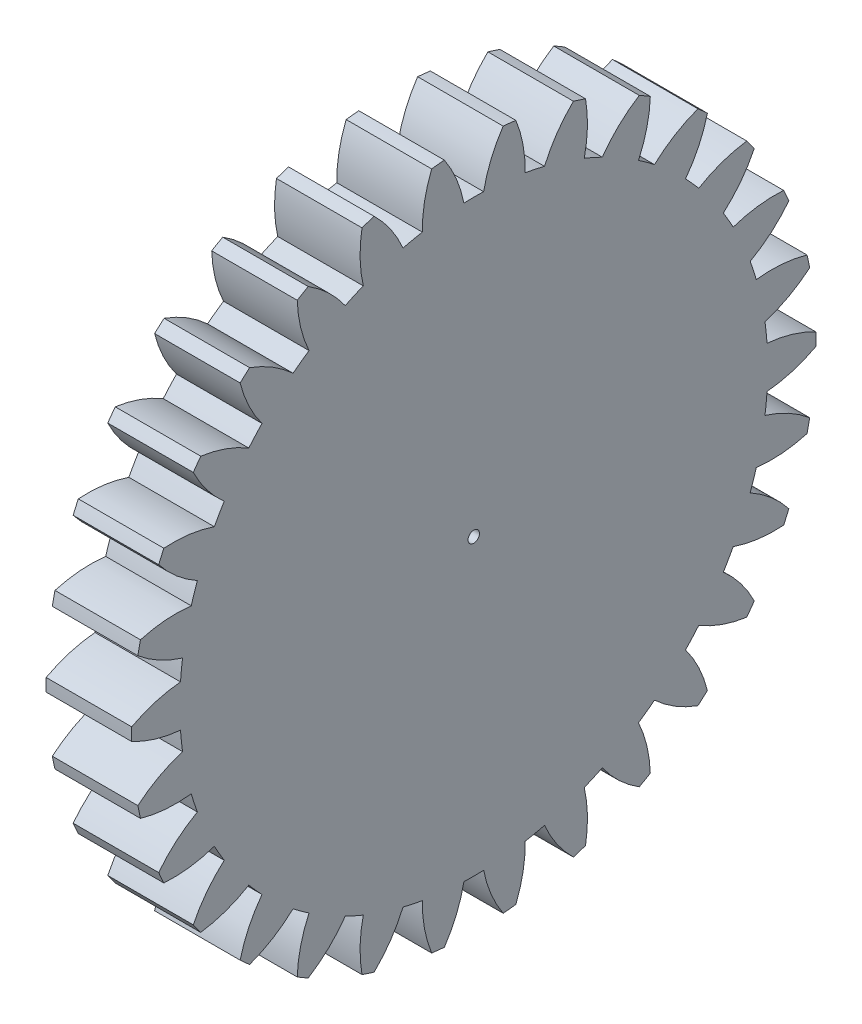
SolidWorks part; units mm, degrees
ref_plane "Plane1" through (0, 0, 0) normal (0, 0, 1) x (1, 0, 0)
ref_plane "Plane2" through (0, 0, 0) normal (0, 1, 0) x (1, 0, 0)
ref_plane "Plane3" through (0, 0, 0) normal (1, 0, 0) x (0, 0, -1)
sketch "HoldingSke" plane through (0, 0, 0) normal (0, 1, 0) x (1, 0, 0)
  line L0 (0, 0) -> (0.5774, -0.3333)
  line L1 (-15, 0) -> (100, 0) construction
  line L2 (0, 0) -> (-2.1039, 2.3779)
  line L3 (0, 0) -> (-11.863, 4.5341)
  line L4 (0, 0) -> (7.479, 4.318)
  line L5 (0, 0) -> (-46.8476, -17.4728)
  line L6 (0, 0) -> (-4.9738, -3.3558)
  line L7 (-2.1039, 2.3779) -> (8.6586, 51.2059)
  line L8 (-76.2, 54.61) -> (-76.1, 54.61)
  line L9 (-71.009, 38.7566) -> (-53.1078, 45.2721)
  line L10 (-76.2, 71.12) -> (104.1128, 71.12)
  line L11 (0, 0) -> (-6, 0)
  line L12 (-76.2, 101.6) -> (-76.147, 101.6)
  line L13 (24.9733, 27.94) -> (52.9518, 28.4284)
  line L14 (24.9733, 27.94) -> (24.9743, 27.94)
  line L15 (24.9733, 27.94) -> (100.4006, 29.5858)
  line L16 (-63.627, -1.5) -> (-12.827, -1.5)
  circle A0 centre (0, 0) radius 0.4
  circle A1 centre (0, 0) radius 20.624
  circle A2 centre (0, 0) radius 37.5
  circle A3 centre (0, 0) radius 0.4
  dimension "MHD" = 41.248
  dimension "Hub_dia" = 75
  dimension "Bore" = 0.8
  dimension "MBD" = 0.8
  dimension "Num_teeth" = 30
  dimension "Pitch_radius" = 180.3128
  dimension "Pitch" = 0.6667
  dimension "Width" = 6
  dimension "Overall_len" = 50
  dimension "Show_teeth" = 30
  dimension "Thickness" = 6
  dimension "OAL" = 50.0001
  dimension "T_dim" = 0.1
  dimension "Ap" = 20
  dimension "H" = 19.05
  dimension "Backlash" = 0.053
  dimension "Addendum_fac" = 1
  dimension "Dedendum_fac" = 1.25
  dimension "Clearance_fac" = 0.25
  dimension "Dedendum_add" = 0.001
  dimension "Module" = 1.5
sketch "BasProSke" plane through (0, 0, 0) normal (0, 1, 0) x (1, 0, 0)
  line L0 (-10, 0) -> (60, 0) construction
  line L1 (0, 0) -> (0, 24)
  line L2 (0, 0) -> (6, 0)
  line L3 (6, 0) -> (6, 24)
  line L4 (6, 24) -> (0, 24)
  dimension "Diameter" = 48
  dimension "Thickness" = 6
revolve "Base-Revolve" add sketch "BasProSke" angle 360 about L0
sketch "TooCutSke" plane through (0, 0, 0) normal (1, 0, 0) x (0, 0, -1)
  line L1 (0, 0) -> (0, 107) construction
  line L2 (0, 0) -> (-1.2703, 22.4641) construction
  line L3 (0, 0) -> (-4.6983, 44.7014) construction
  line L4 (-1.2703, 22.4641) -> (-2.3492, 22.3507) construction
  arc A0 (0.6933, 20.6123) -> (-0.6933, 20.6123) centre (0, 0) ccw
  arc A1 (2.0805, 23.9351) -> (-2.0805, 23.9351) centre (0, 0) ccw
  circle A2 centre (0, 0) radius 22.5 construction
  circle A3 centre (0, 0) radius 21.1431 construction
  arc A4 (-0.6933, 20.6123) -> (-2.0805, 23.9351) centre (-9.5243, 18.8764) ccw
  arc A5 (2.0805, 23.9351) -> (0.6933, 20.6123) centre (9.5243, 18.8764) ccw
  dimension "Root_dia" = 41.248
  dimension "Overcut_dia" = 48.0508
  dimension "Pitch_dia" = 45
  dimension "Base_dia" = 42.2862
  dimension "Flank_rad" = 9
  dimension "Half_ang" = 6
  dimension "Half_CT" = 1.0848
extrude "ToothCut" cut sketch "TooCutSke" along normal through all
fillet "Breaks" [suppressed] radius 0.03 tangent propagation no
fillet "RootFillets" [suppressed] radius 0.376
pattern_circular "TeethCuts" count 30 every 12 about axis through (-10, 0, 0) along (1, 0, 0) of "ToothCut", "RootFillets", "Breaks"
sketch "HubNeaOneSke" plane through (0, 0, 0) normal (-1, 0, 0) x (0, 0, 1)
  circle A0 centre (0, 0) radius 20.624
  dimension "Diameter" = 41.248
extrude "HubNearOne" [suppressed] add sketch "HubNeaOneSke" along normal blind 44.0001
sketch "HubNeaBotSke" plane through (0, 0, 0) normal (-1, 0, 0) x (0, 0, 1)
  circle A0 centre (0, 0) radius 20.624
  dimension "Diameter" = 41.248
extrude "HubNearBoth" [suppressed] add sketch "HubNeaBotSke" along normal blind 22
ref_plane "FarPln" through (6, 0, 0) normal (1, 0, 0) x (0, 0, -1)
sketch "HubFarSke" plane through (6, 0, 0) normal (1, 0, 0) x (0, 0, -1)
  circle A0 centre (0, 0) radius 20.624
  dimension "Diameter" = 41.248
extrude "HubFar" [suppressed] add sketch "HubFarSke" along normal blind 22
sketch "BorSke" plane through (0, 0, 0) normal (1, 0, 0) x (0, 0, -1)
  circle A0 centre (0, 0) radius 0.4
  dimension "Diameter" = 0.8
extrude "Bore" cut sketch "BorSke" along normal mid plane 100.0001
sketch "KeySke" plane through (0, 0, 0) normal (1, 0, 0) x (0, 0, -1)
  line L0 (-0.05, 0) -> (-0.05, 0.5)
  line L1 (-0.05, 0.5) -> (0.05, 0.5)
  line L2 (0.05, 0.5) -> (0.05, 0)
  line L3 (0, 0) -> (0, 34) construction
  line L4 (-0.05, 0) -> (0.05, 0)
  dimension "Offset" = 0.5
  dimension "Width" = 0.1
extrude "Keyway" [suppressed] cut sketch "KeySke" along normal mid plane 100.0001
pattern_circular "Keyway2" [suppressed] count 2 every 90 about axis through (-10, 0, 0) along (1, 0, 0)
equation "' \"Module@HoldingSke\" = 6.35"
equation "' \"Num_teeth@HoldingSke\" = 12"
equation "' \"Ap@HoldingSke\" =  20"
equation "' \"Width@HoldingSke\" = 0.5 * 25.4"
equation "' \"Hub_dia@HoldingSke\"= 1 * 25.4"
equation "' \"Overall_len@HoldingSke\" = 1.0 * 25.4"
equation "' \"Bore@HoldingSke\" = 0.75 * 25.4"
equation "' \"T_dim@HoldingSke\" = 0.1 * 25.4"
equation "' \"Width@KeySke\" = 0.25 * 25.4"
equation "' \"Show_teeth@HoldingSke\" = 13"
equation "' \"Backlash@HoldingSke\" = 0.009 * 25.4"
equation "' \"Addendum_fac@HoldingSke\" = 1.0"
equation "' \"Dedendum_fac@HoldingSke\" = 1.25"
equation "' \"Dedendum_add@HoldingSke\" = 0.00005 * 25.4"
equation "' \"Clearance_fac@HoldingSke\" = 0.25"
equation "\"Pitch@HoldingSke\" = 1 / \"Module@HoldingSke\""
equation "\"Overcut_dia@TooCutSke\" = (\"Num_teeth@HoldingSke\" + 2 * \"Addendum_fac@HoldingSke\") / \"Pitch@HoldingSke\" + 0.002 * 25.4"
equation "\"Pitch_dia@TooCutSke\" = \"Num_teeth@HoldingSke\" / \"Pitch@HoldingSke\""
equation "\"Base_dia@TooCutSke\" = \"Num_teeth@HoldingSke\" / \"Pitch@HoldingSke\" * cos((\"Ap@HoldingSke\"  * 3.14159265 / 180))"
equation "\"Root_dia@TooCutSke\" = (\"Num_teeth@HoldingSke\" + 2) / \"Pitch@HoldingSke\" - 2 * (\"Addendum_fac@HoldingSke\" + \"Dedendum_fac@HoldingSke\") / \"Pitch@HoldingSke\" - \"Dedendum_add@HoldingSke\" * 2"
equation "\"Half_ang@TooCutSke\" = 180 / \"Num_teeth@HoldingSke\""
equation "\"Half_CT@TooCutSke\" = \"Num_teeth@HoldingSke\" / \"Pitch@HoldingSke\" * sin((3.14159265 / 2 / \"Num_teeth@HoldingSke\")) / 2 - 7 * \"Backlash@HoldingSke\" / 4"
equation "\"Flank_rad@TooCutSke\" = \"Num_teeth@HoldingSke\" / \"Pitch@HoldingSke\" / 5"
equation "\"Radius@RootFillets\" = \"Clearance_fac@HoldingSke\" / \"Pitch@HoldingSke\" + \"Dedendum_add@HoldingSke\""
equation "\"Break_rad@Breaks\" = 0.02 / \"Pitch@HoldingSke\""
equation "\"Thickness@HoldingSke\" = \"Width@HoldingSke\""
equation "\"OAL@HoldingSke\" = \"Thickness@HoldingSke\""
equation "\"MHD@HoldingSke\" = (\"Num_teeth@HoldingSke\" + 2) / \"Pitch@HoldingSke\" - 2 * (\"Addendum_fac@HoldingSke\" + \"Dedendum_fac@HoldingSke\")  / \"Pitch@HoldingSke\" - \"Dedendum_add@HoldingSke\" * 2"
equation "\"MBD@HoldingSke\" = (\"Num_teeth@HoldingSke\" + 2) / \"Pitch@HoldingSke\" - 2 * (\"Addendum_fac@HoldingSke\" + \"Dedendum_fac@HoldingSke\")  / \"Pitch@HoldingSke\" - \"Dedendum_add@HoldingSke\" * 2 - 0.002 * 25.4"
equation "\"MHD@HoldingSke\" = ((sgn( \"MHD@HoldingSke\" - \"Hub_dia@HoldingSke\" )-1)*( \"MHD@HoldingSke\" - \"Hub_dia@HoldingSke\" ))/-2+ \"Hub_dia@HoldingSke\""
equation "\"MBD@HoldingSke\" = ((sgn( \"MBD@HoldingSke\" - \"Bore@HoldingSke\" )-1)*( \"MBD@HoldingSke\" - \"Bore@HoldingSke\" ))/-2+ \"Bore@HoldingSke\""
equation "\"OAL@HoldingSke\" = ((sgn( \"OAL@HoldingSke\" - \"Overall_len@HoldingSke\" )+1)*( \"OAL@HoldingSke\" - \"Overall_len@HoldingSke\" ))/2 + \"Overall_len@HoldingSke\" + 0.000002 * 25.4"
equation "\"Num_teeth@TeethCuts\" = int( \"Show_teeth@HoldingSke\" ) + 1"
equation "\"Num_teeth@TeethCuts\" = ((sgn( \"Num_teeth@TeethCuts\" - \"Num_teeth@HoldingSke\" )-1)*( \"Num_teeth@TeethCuts\" - \"Num_teeth@HoldingSke\" ))/-2+ \"Num_teeth@HoldingSke\""
equation "\"Num_teeth@TeethCuts\" = ((sgn( \"Num_teeth@TeethCuts\" - 2.0)+1)*( \"Num_teeth@TeethCuts\" - 2.0))/2 +2.0"
equation "\"Angle@TeethCuts\" = 360.0 / \"Num_teeth@HoldingSke\""
equation "\"Diameter@BasProSke\" = (\"Num_teeth@HoldingSke\" + 2 * \"Addendum_fac@HoldingSke\") / \"Pitch@HoldingSke\""
equation "\"Thickness@BasProSke\"  = \"Thickness@HoldingSke\""
equation "' \"Fillet_rad@BasProSke\" =  \"Thickness@HoldingSke\" * 0.05"
equation "\"MHD@HoldingSke\" = ((sgn( \"MHD@HoldingSke\" - \"Root_dia@TooCutSke\" )-1)*( \"MHD@HoldingSke\" - \"Root_dia@TooCutSke\" ))/-2+ \"Root_dia@TooCutSke\""
equation "\"Diameter@HubNeaOneSke\" = \"MHD@HoldingSke\""
equation "\"Length@HubNearOne\" = \"OAL@HoldingSke\" - \"Thickness@BasProSke\""
equation "\"Diameter@HubNeaBotSke\" = \"MHD@HoldingSke\""
equation "\"Length@HubNearBoth\" = ( \"OAL@HoldingSke\" - \"Thickness@BasProSke\" ) / 2.0"
equation "\"Thickness@FarPln\" = \"Thickness@BasProSke\""
equation "\"Diameter@HubFarSke\" = \"MHD@HoldingSke\""
equation "\"Length@HubFar\" = ( \"OAL@HoldingSke\" - \"Thickness@BasProSke\" ) / 2.0"
equation "\"Diameter@BorSke\" = \"MBD@HoldingSke\""
equation "\"D1@Bore\" = \"OAL@HoldingSke\" * 2.0"
equation "\"D1@Keyway\" = \"OAL@HoldingSke\" * 2.0"
equation "\"Offset@KeySke\" = \"T_dim@HoldingSke\" + \"MBD@HoldingSke\" / 2.0"
